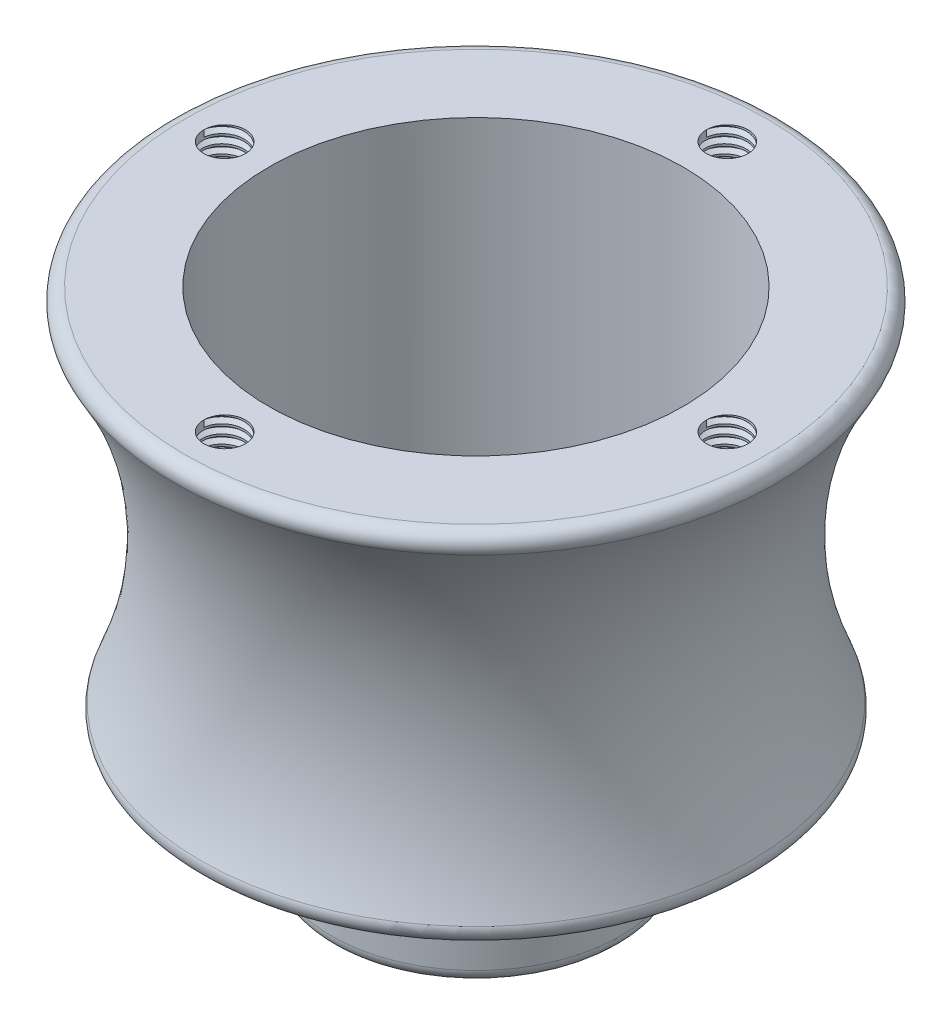
SolidWorks part; units mm, degrees
ref_plane "Alzado" through (0, 0, 0) normal (0, 0, 1) x (1, 0, 0)
ref_plane "Planta" through (0, 0, 0) normal (0, 1, 0) x (1, 0, 0)
ref_plane "Vista lateral" through (0, 0, 0) normal (1, 0, 0) x (0, 0, -1)
sketch "Croquis1" plane through (0, 0, 0) normal (0, 0, 1) x (1, 0, 0)
  line L0 (0, 0) -> (0, 43.5196) construction
  line L5 (25, 40) -> (16.5, 40)
  line L6 (16.5, 15) -> (16.5, 40)
  line L8 (16.5, 15) -> (6.35, 15)
  line L9 (6.35, 15) -> (6.35, 0)
  line L10 (6.35, 0) -> (11.5, 0)
  line L11 (11.5, 0) -> (11.5, 10)
  line L12 (11.5, 10) -> (22.5, 10)
  line L13 (18, 40) -> (18, 35) construction
  line L14 (18, 35) -> (22, 35) construction
  line L15 (22, 35) -> (22, 40) construction
  line L16 (18, 35) -> (20, 33.8453) construction
  line L17 (20, 33.8453) -> (22, 35) construction
  line L18 (20, 35) -> (20, 40) construction
  arc A4 (25, 40) -> (22.5, 10) centre (49.611, 22.8449) ccw
  point P4 (30, 35)
  point P5 (19.611, 22.8449)
  point P11 (23.0494, 10)
  point P20 (20, 35)
  dimension "D6" = 5.389
  dimension "D8" = 19.611
  dimension "D9" = 6.35
  dimension "D10" = 15
  dimension "D4" = 30
  dimension "D14" = 4
  dimension "D1" = 16.5
  dimension "D2" = 25
  dimension "D3" = 2.5
  dimension "D5" = 40
  dimension "D7" = 3.111
  dimension "D11" = 11.5
  dimension "D12" = 10
  dimension "D13" = 60
  dimension "D15" = 5
  dimension "D16" = 30
  dimension "D17" = 2
  dimension "D18" = 20
  dimension "D19" = 1.5
revolve "Revolución1" add sketch "Croquis1" angle 360 about L0
fillet "Redondeo4" radius 1 1 edges at (0, 10, -11.5)
fillet "Redondeo3" radius 1 4 edges at (0, 0, -6.35) (0, 15, -6.35) (0, 15, -16.5) (0, 0, -11.5)
fillet "Redondeo5" radius 1 2 edges at (0, 40, -25) (0, 10, -22.5)
sketch "Croquis3" plane through (0, 40, 0) normal (0, 1, 0) x (1, 0, 0)
  circle A0 centre (0, 0) radius 23.1533 construction
  circle A2 centre (0, 0) radius 23.1533 construction
  circle A4 centre (0, 0) radius 20 construction
  point P6 (0, 20)
  point P7 (0, -20)
  point P8 (20, 0)
  point P9 (-20, 0)
  point P10 (-35.4867, 7.4356)
  dimension "D1" = 40
hole_wizard "Perforador para roscar Helicoil de M41" positions "Croquis4" profile "Croquis5" hole size "M4x0.7" standard "Ansi Metric"
sketch "Croquis4" plane through (0, 40, 0) normal (0, 1, 0) x (1, 0, 0)
  point P0 (0, 20)
sketch "Croquis5" plane through (0, 40, -20) normal (1, 0, 0) x (0, 0, 1)
  line L0 (0, 0) -> (0, 5.9914)
  line L1 (0, 5.9914) -> (1.65, 5)
  line L2 (1.65, 5) -> (1.65, 0)
  line L5 (1.65, 0) -> (0, 0)
  line L10 (0, 5.9914) -> (-1.65, 5) construction
  line L11 (0, -6.35) -> (0, 107.95) construction
  dimension "Diámetro de taladro" = 3.3
  dimension "Profundidad de taladro" = 5
  dimension "Ángulo de perforador" = 118
pattern_circular "MatrizC1" count 4 over 360 about axis through (0, 38.4789, 0) along (0, -1, 0) of "Perforador para roscar Helicoil de M41"
thread "Rosca1" pitch 0.7 method cut profile "Perfil de rosca1" start angle 0, offset 0, length 5, pitch 0.7, diameter 3.3
ref_plane "Plano1" through (-1.65, 40, -20) normal (0, 0, 1) x (-1, 0, 0)
sketch "Perfil de rosca1" plane through (-1.65, 40, -20) normal (0, 0, 1) x (-1, 0, 0)
  line L0 (0, 0) -> (0, 0.7) construction
  line L1 (0, 0) -> (0.3789, 0.2187)
  line L2 (0.3789, 0.2187) -> (0.3789, 0.3062)
  line L3 (0.3789, 0.3062) -> (0, 0.525)
  line L4 (0.3789, 0.2625) -> (0, 0.2625) construction
  line L11 (0, 0) -> (0, 0.525)
  point P2 (0, 0)
  dimension "Pitch" = 0.7
  dimension "Profile_Angle" = 60
  dimension "Profile_Land" = 0.0875
  dimension "Profile_Height" = 0.3789
thread "Rosca2" pitch 0.7 method cut profile "Perfil de rosca2" start angle 0, offset 0, length 5, pitch 0.7, diameter 3.3
ref_plane "Plano2" through (18.35, 40, 0) normal (0, 0, 1) x (-1, 0, 0)
sketch "Perfil de rosca2" plane through (18.35, 40, 0) normal (0, 0, 1) x (-1, 0, 0)
  line L0 (0, 0) -> (0, 0.7) construction
  line L1 (0, 0) -> (0.3789, 0.2187)
  line L2 (0.3789, 0.2187) -> (0.3789, 0.3062)
  line L3 (0.3789, 0.3062) -> (0, 0.525)
  line L4 (0.3789, 0.2625) -> (0, 0.2625) construction
  line L11 (0, 0) -> (0, 0.525)
  point P2 (0, 0)
  dimension "Pitch" = 0.7
  dimension "Profile_Angle" = 60
  dimension "Profile_Land" = 0.0875
  dimension "Profile_Height" = 0.3789
thread "Rosca3" pitch 0.7 method cut profile "Perfil de rosca3" start angle 0, offset 0, length 5, pitch 0.7, diameter 3.3
ref_plane "Plano3" through (-1.65, 40, 20) normal (0, 0, 1) x (-1, 0, 0)
sketch "Perfil de rosca3" plane through (-1.65, 40, 20) normal (0, 0, 1) x (-1, 0, 0)
  line L0 (0, 0) -> (0, 0.7) construction
  line L1 (0, 0) -> (0.3789, 0.2187)
  line L2 (0.3789, 0.2187) -> (0.3789, 0.3062)
  line L3 (0.3789, 0.3062) -> (0, 0.525)
  line L4 (0.3789, 0.2625) -> (0, 0.2625) construction
  line L11 (0, 0) -> (0, 0.525)
  point P2 (0, 0)
  dimension "Pitch" = 0.7
  dimension "Profile_Angle" = 60
  dimension "Profile_Land" = 0.0875
  dimension "Profile_Height" = 0.3789
thread "Rosca4" pitch 0.7 method cut profile "Perfil de rosca4" start angle 0, offset 0, length 5, pitch 0.7, diameter 3.3
ref_plane "Plano4" through (-21.65, 40, 0) normal (0, 0, 1) x (-1, 0, 0)
sketch "Perfil de rosca4" plane through (-21.65, 40, 0) normal (0, 0, 1) x (-1, 0, 0)
  line L0 (0, 0) -> (0, 0.7) construction
  line L1 (0, 0) -> (0.3789, 0.2187)
  line L2 (0.3789, 0.2187) -> (0.3789, 0.3062)
  line L3 (0.3789, 0.3062) -> (0, 0.525)
  line L4 (0.3789, 0.2625) -> (0, 0.2625) construction
  line L11 (0, 0) -> (0, 0.525)
  point P2 (0, 0)
  dimension "Pitch" = 0.7
  dimension "Profile_Angle" = 60
  dimension "Profile_Land" = 0.0875
  dimension "Profile_Height" = 0.3789
ref_plane "Plano5" through (-11.5, 0, 0) normal (-1, 0, 0) x (0, 0, 1)
